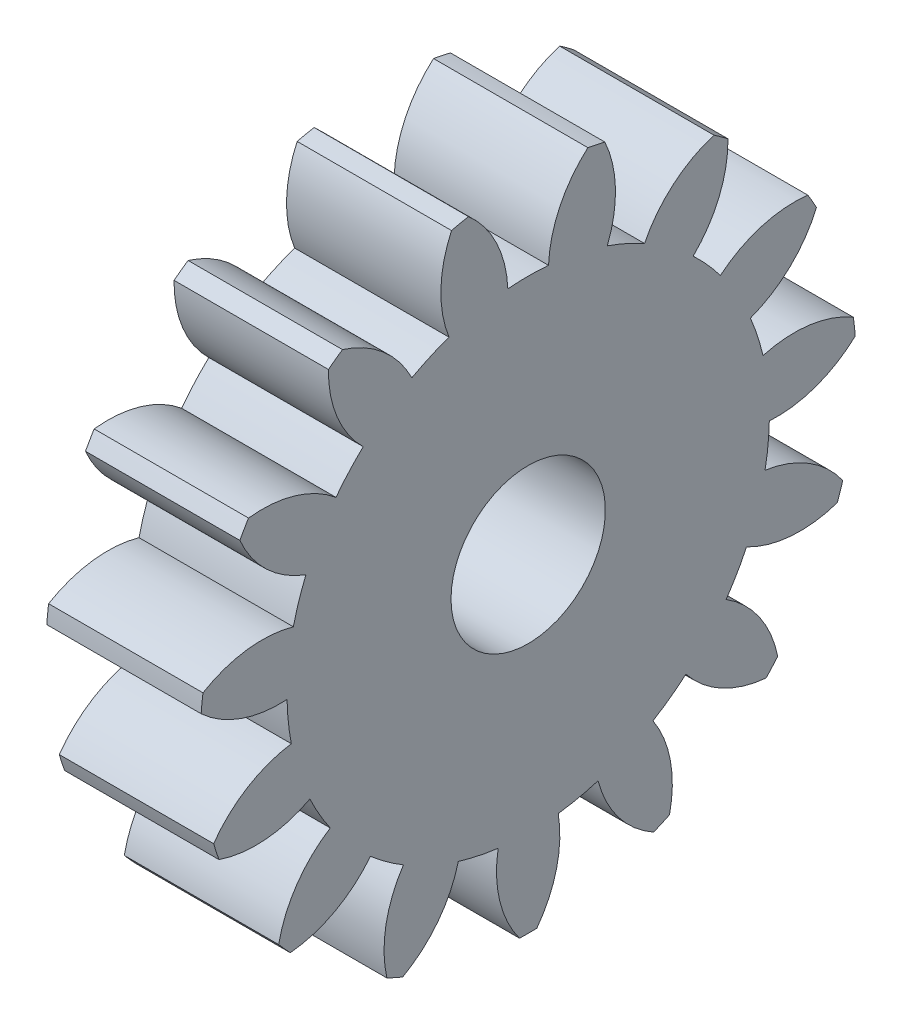
SolidWorks part; units mm, degrees
ref_plane "Plane1" through (0, 0, 0) normal (0, 0, 1) x (1, 0, 0)
ref_plane "Plane2" through (0, 0, 0) normal (0, 1, 0) x (1, 0, 0)
ref_plane "Plane3" through (0, 0, 0) normal (1, 0, 0) x (0, 0, -1)
sketch "HoldingSke" plane through (0, 0, 0) normal (0, 1, 0) x (1, 0, 0)
  line L0 (0, 0) -> (0.644, -0.1725)
  line L1 (-15, 0) -> (100, 0) construction
  line L2 (0, 0) -> (-2.1039, 2.3779)
  line L3 (0, 0) -> (-11.863, 4.5341)
  line L4 (0, 0) -> (8.3417, 2.2352)
  line L5 (0, 0) -> (-46.8476, -17.4728)
  line L6 (0, 0) -> (-4.9738, -3.3558)
  line L7 (-2.1039, 2.3779) -> (8.6586, 51.2059)
  line L8 (-76.2, 54.61) -> (-75.2, 54.61)
  line L9 (-71.009, 38.7566) -> (-53.1078, 45.2721)
  line L10 (-76.2, 71.12) -> (104.1128, 71.12)
  line L11 (0, 0) -> (-6, 0)
  line L12 (-76.2, 101.6) -> (-76.147, 101.6)
  line L13 (24.9733, 27.94) -> (52.9518, 28.4284)
  line L14 (24.9733, 27.94) -> (24.9743, 27.94)
  line L15 (24.9733, 27.94) -> (100.4006, 29.5858)
  line L16 (-63.627, -1.5) -> (-12.827, -1.5)
  circle A0 centre (0, 0) radius 3
  circle A1 centre (0, 0) radius 9.374
  circle A2 centre (0, 0) radius 37.5
  circle A3 centre (0, 0) radius 3
  dimension "Num_teeth" = 15
  dimension "Pitch_radius" = 180.3128
  dimension "Width" = 6
  dimension "Thickness" = 6
sketch "BasProSke" plane through (0, 0, 0) normal (0, 1, 0) x (1, 0, 0)
  line L0 (-10, 0) -> (60, 0) construction
  line L1 (0, 0) -> (0, 12.75)
  line L2 (0, 0) -> (6, 0)
  line L3 (6, 0) -> (6, 12.75)
  line L4 (6, 12.75) -> (0, 12.75)
  dimension "Thickness" = 6
  dimension "Diameter" = 25.5
revolve "Base-Revolve" add sketch "BasProSke" angle 360 about L0
sketch "TooCutSke" plane through (0, 0, 0) normal (1, 0, 0) x (0, 0, -1)
  line L1 (0, 0) -> (0, 107) construction
  line L2 (0, 0) -> (-1.2686, 11.1782) construction
  line L3 (0, 0) -> (-4.6563, 21.9061) construction
  line L4 (-1.2686, 11.1782) -> (-2.3281, 10.953) construction
  arc A0 (0.7915, 9.3405) -> (-0.7915, 9.3405) centre (0, 0) ccw
  arc A1 (2.3447, 12.5584) -> (-2.3447, 12.5584) centre (0, 0) ccw
  circle A2 centre (0, 0) radius 11.25 construction
  circle A3 centre (0, 0) radius 10.5715 construction
  arc A4 (-0.7915, 9.3405) -> (-2.3447, 12.5584) centre (-5.2877, 9.1541) ccw
  arc A5 (2.3447, 12.5584) -> (0.7915, 9.3405) centre (5.2877, 9.1541) ccw
extrude "ToothCut" cut sketch "TooCutSke" along normal through all
fillet "Breaks" [suppressed] radius 0.03 tangent propagation no
fillet "RootFillets" [suppressed] radius 0.376
pattern_circular "TeethCuts" count 15 every 24 about axis through (-10, 0, 0) along (1, 0, 0) of "ToothCut", "RootFillets", "Breaks"
sketch "HubNeaOneSke" plane through (0, 0, 0) normal (-1, 0, 0) x (0, 0, 1)
  circle A0 centre (0, 0) radius 9.374
  dimension "Diameter" = 18.748
extrude "HubNearOne" [suppressed] add sketch "HubNeaOneSke" along normal blind 44.0001
sketch "HubNeaBotSke" plane through (0, 0, 0) normal (-1, 0, 0) x (0, 0, 1)
  circle A0 centre (0, 0) radius 9.374
  dimension "Diameter" = 18.748
extrude "HubNearBoth" [suppressed] add sketch "HubNeaBotSke" along normal blind 22
ref_plane "FarPln" through (6, 0, 0) normal (1, 0, 0) x (0, 0, -1)
sketch "HubFarSke" plane through (6, 0, 0) normal (1, 0, 0) x (0, 0, -1)
  circle A0 centre (0, 0) radius 9.374
  dimension "Diameter" = 18.748
extrude "HubFar" [suppressed] add sketch "HubFarSke" along normal blind 22
sketch "BorSke" plane through (0, 0, 0) normal (1, 0, 0) x (0, 0, -1)
  circle A0 centre (0, 0) radius 3
  dimension "Diameter" = 6
extrude "Bore" cut sketch "BorSke" along normal mid plane 100.0001
sketch "KeySke" plane through (0, 0, 0) normal (1, 0, 0) x (0, 0, -1)
  line L0 (-1, 0) -> (-1, 4)
  line L1 (-1, 4) -> (1, 4)
  line L2 (1, 4) -> (1, 0)
  line L3 (0, 0) -> (0, 34) construction
  line L4 (-1, 0) -> (1, 0)
  dimension "Width" = 2
extrude "Keyway" [suppressed] cut sketch "KeySke" along normal mid plane 100.0001
pattern_circular "Keyway2" [suppressed] count 2 every 90 about axis through (-10, 0, 0) along (1, 0, 0) reverse direction yes
equation "' \"Module@HoldingSke\" = 6.35"
equation "' \"Num_teeth@HoldingSke\" = 12"
equation "' \"Ap@HoldingSke\" =  20"
equation "' \"Ap@HoldingSke\" = 20"
equation "' \"Width@HoldingSke\" = 0.5 * 25.4"
equation "' \"Hub_dia@HoldingSke\"= 1 * 25.4"
equation "' \"Hub_dia@HoldingSke\" = 1 * 25.4"
equation "' \"Overall_len@HoldingSke\" = 1.0 * 25.4"
equation "' \"Bore@HoldingSke\" = 0.75 * 25.4"
equation "' \"T_dim@HoldingSke\" = 0.1 * 25.4"
equation "' \"Width@KeySke\" = 0.25 * 25.4"
equation "' \"Show_teeth@HoldingSke\" = 13"
equation "' \"Backlash@HoldingSke\" = 0.009 * 25.4"
equation "' \"Addendum_fac@HoldingSke\" = 1.0"
equation "' \"Dedendum_fac@HoldingSke\" = 1.25"
equation "' \"Dedendum_add@HoldingSke\" = 0.00005 * 25.4"
equation "' \"Clearance_fac@HoldingSke\" = 0.25"
equation "\"Pitch@HoldingSke\" = 1 / \"Module@HoldingSke\""
equation "\"Overcut_dia@TooCutSke\" = (\"Num_teeth@HoldingSke\" + 2 * \"Addendum_fac@HoldingSke\") / \"Pitch@HoldingSke\" + 0.002 * 25.4"
equation "\"Pitch_dia@TooCutSke\" = \"Num_teeth@HoldingSke\" / \"Pitch@HoldingSke\""
equation "\"Base_dia@TooCutSke\" = \"Num_teeth@HoldingSke\" / \"Pitch@HoldingSke\" * cos((\"Ap@HoldingSke\"  * 3.14159265 / 180))"
equation "\"Root_dia@TooCutSke\" = (\"Num_teeth@HoldingSke\" + 2) / \"Pitch@HoldingSke\" - 2 * (\"Addendum_fac@HoldingSke\" + \"Dedendum_fac@HoldingSke\") / \"Pitch@HoldingSke\" - \"Dedendum_add@HoldingSke\" * 2"
equation "\"Half_ang@TooCutSke\" = 180 / \"Num_teeth@HoldingSke\""
equation "\"Half_CT@TooCutSke\" = \"Num_teeth@HoldingSke\" / \"Pitch@HoldingSke\" * sin((3.14159265 / 2 / \"Num_teeth@HoldingSke\")) / 2 - 7 * \"Backlash@HoldingSke\" / 4"
equation "\"Flank_rad@TooCutSke\" = \"Num_teeth@HoldingSke\" / \"Pitch@HoldingSke\" / 5"
equation "\"Radius@RootFillets\" = \"Clearance_fac@HoldingSke\" / \"Pitch@HoldingSke\" + \"Dedendum_add@HoldingSke\""
equation "\"Break_rad@Breaks\" = 0.02 / \"Pitch@HoldingSke\""
equation "\"Thickness@HoldingSke\" = \"Width@HoldingSke\""
equation "\"OAL@HoldingSke\" = \"Thickness@HoldingSke\""
equation "\"MHD@HoldingSke\" = (\"Num_teeth@HoldingSke\" + 2) / \"Pitch@HoldingSke\" - 2 * (\"Addendum_fac@HoldingSke\" + \"Dedendum_fac@HoldingSke\")  / \"Pitch@HoldingSke\" - \"Dedendum_add@HoldingSke\" * 2"
equation "\"MBD@HoldingSke\" = (\"Num_teeth@HoldingSke\" + 2) / \"Pitch@HoldingSke\" - 2 * (\"Addendum_fac@HoldingSke\" + \"Dedendum_fac@HoldingSke\")  / \"Pitch@HoldingSke\" - \"Dedendum_add@HoldingSke\" * 2 - 0.002 * 25.4"
equation "\"MHD@HoldingSke\" = ((sgn( \"MHD@HoldingSke\" - \"Hub_dia@HoldingSke\" )-1)*( \"MHD@HoldingSke\" - \"Hub_dia@HoldingSke\" ))/-2+ \"Hub_dia@HoldingSke\""
equation "\"MBD@HoldingSke\" = ((sgn( \"MBD@HoldingSke\" - \"Bore@HoldingSke\" )-1)*( \"MBD@HoldingSke\" - \"Bore@HoldingSke\" ))/-2+ \"Bore@HoldingSke\""
equation "\"OAL@HoldingSke\" = ((sgn( \"OAL@HoldingSke\" - \"Overall_len@HoldingSke\" )+1)*( \"OAL@HoldingSke\" - \"Overall_len@HoldingSke\" ))/2 + \"Overall_len@HoldingSke\" + 0.000002 * 25.4"
equation "\"Num_teeth@TeethCuts\" = int( \"Show_teeth@HoldingSke\" ) + 1"
equation "\"Num_teeth@TeethCuts\" = ((sgn( \"Num_teeth@TeethCuts\" - \"Num_teeth@HoldingSke\" )-1)*( \"Num_teeth@TeethCuts\" - \"Num_teeth@HoldingSke\" ))/-2+ \"Num_teeth@HoldingSke\""
equation "\"Num_teeth@TeethCuts\" = ((sgn( \"Num_teeth@TeethCuts\" - 2.0)+1)*( \"Num_teeth@TeethCuts\" - 2.0))/2 +2.0"
equation "\"Angle@TeethCuts\" = 360.0 / \"Num_teeth@HoldingSke\""
equation "\"Diameter@BasProSke\" = (\"Num_teeth@HoldingSke\" + 2 * \"Addendum_fac@HoldingSke\") / \"Pitch@HoldingSke\""
equation "\"Thickness@BasProSke\"  = \"Thickness@HoldingSke\""
equation "' \"Fillet_rad@BasProSke\" =  \"Thickness@HoldingSke\" * 0.05"
equation "' \"Fillet_rad@BasProSke\" = \"Thickness@HoldingSke\" * 0.05"
equation "\"MHD@HoldingSke\" = ((sgn( \"MHD@HoldingSke\" - \"Root_dia@TooCutSke\" )-1)*( \"MHD@HoldingSke\" - \"Root_dia@TooCutSke\" ))/-2+ \"Root_dia@TooCutSke\""
equation "\"Diameter@HubNeaOneSke\" = \"MHD@HoldingSke\""
equation "\"Length@HubNearOne\" = \"OAL@HoldingSke\" - \"Thickness@BasProSke\""
equation "\"Diameter@HubNeaBotSke\" = \"MHD@HoldingSke\""
equation "\"Length@HubNearBoth\" = ( \"OAL@HoldingSke\" - \"Thickness@BasProSke\" ) / 2.0"
equation "\"Thickness@FarPln\" = \"Thickness@BasProSke\""
equation "\"Diameter@HubFarSke\" = \"MHD@HoldingSke\""
equation "\"Length@HubFar\" = ( \"OAL@HoldingSke\" - \"Thickness@BasProSke\" ) / 2.0"
equation "\"Diameter@BorSke\" = \"MBD@HoldingSke\""
equation "\"D1@Bore\" = \"OAL@HoldingSke\" * 2.0"
equation "\"D1@Keyway\" = \"OAL@HoldingSke\" * 2.0"
equation "\"Offset@KeySke\" = \"T_dim@HoldingSke\" + \"MBD@HoldingSke\" / 2.0"
